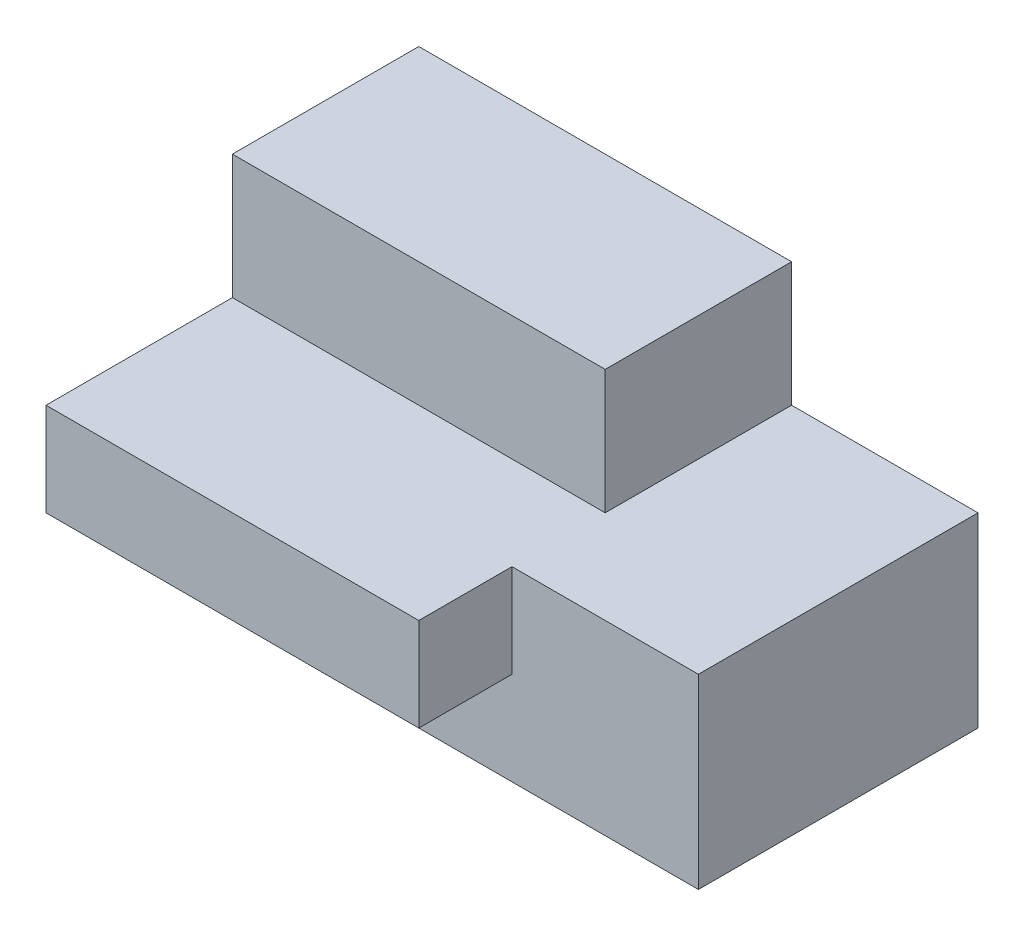
SolidWorks part; units mm, degrees
ref_plane "Front Plane" through (0, 0, 0) normal (0, 0, 1) x (1, 0, 0)
ref_plane "Top Plane" through (0, 0, 0) normal (0, 1, 0) x (1, 0, 0)
ref_plane "Right Plane" through (0, 0, 0) normal (1, 0, 0) x (0, 0, -1)
sketch "Sketch1" plane through (0, 0, 0) normal (0, 0, 1) x (1, 0, 0)
  line L1 (0, 0) -> (72, 0)
  line L2 (0, 0) -> (0, 24)
  line L3 (0, 24) -> (72, 24)
  line L4 (72, 0) -> (72, 24)
  line L5 (0, 24) -> (48, 24)
  line L6 (0, 24) -> (0, 12)
  line L7 (0, 12) -> (48, 12)
  line L8 (48, 24) -> (48, 12)
  line L9 (0, 24) -> (48, 24)
  line L10 (0, 24) -> (0, 40)
  line L11 (0, 40) -> (48, 40)
  line L12 (48, 24) -> (48, 40)
  dimension "D1" = 24
  dimension "D2" = 72
  dimension "D3" = 12
  dimension "D4" = 48
  dimension "D5" = 16
  dimension "D6" = 48
extrude "Boss-Extrude1" add sketch "Sketch1" against normal blind 36 contours L8 L3 L2 L7 | L3 L8 L7 L2 L1 L4 region at (42, 9, 0) region at (24, 18, 0)
extrude "Boss-Extrude2" add sketch "Sketch1<3>" along normal blind 12 contours L8 L3 L2 L7 region at (24, 18, 0)
sketch "Sketch1<3>" plane through (0, 0, 0) normal (0, 0, 1) x (1, 0, 0) same geometry as "Sketch1"
extrude "Boss-Extrude4" add sketch "Sketch1<5>" against normal blind 24 from offset 12 contours L3 L12 L11 L10 region at (24, 32, 0) offset against normal yes
sketch "Sketch1<5>" plane through (0, 0, 0) normal (0, 0, 1) x (1, 0, 0) same geometry as "Sketch1"
